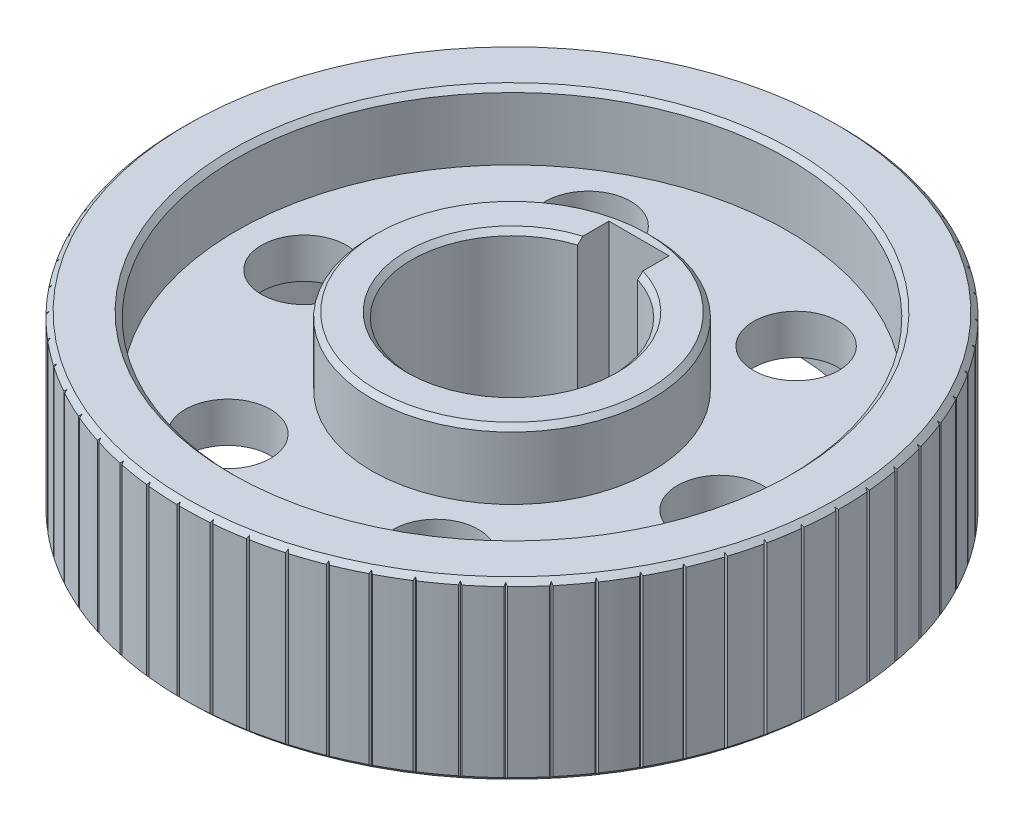
SolidWorks part; units mm, degrees
ref_plane "前视基准面" through (0, 0, 0) normal (0, 0, 1) x (1, 0, 0)
ref_plane "上视基准面" through (0, 0, 0) normal (0, 1, 0) x (1, 0, 0)
ref_plane "右视基准面" through (0, 0, 0) normal (1, 0, 0) x (0, 0, -1)
other "Configuration Table"
sketch "草图2" plane through (0, 0, 0) normal (0, 1, 0) x (1, 0, 0)
  circle A0 centre (0, 0) radius 65.7475
extrude "凸台-拉伸1" add sketch "草图2" along normal blind 35
sketch "草图3" plane through (0, 35, 0) normal (0, 1, 0) x (1, 0, 0)
  line L1 (0, 25.3371) -> (6, 25.3371)
  line L2 (0, 25.3371) -> (-6, 25.3371)
  line L3 (-6, 25.3371) -> (-6, 19.0788)
  line L4 (6, 25.3371) -> (6, 19.0788)
  circle A2 centre (-20.75, 35.9401) radius 8.5
  circle A3 centre (0, 0) radius 65.7475
  circle A4 centre (0, 0) radius 65.7475
  circle A5 centre (20.75, 35.9401) radius 8.5
  circle A6 centre (41.5, 0) radius 8.5
  circle A7 centre (20.75, -35.9401) radius 8.5
  circle A8 centre (-20.75, -35.9401) radius 8.5
  circle A9 centre (-41.5, 0) radius 8.5
  circle A10 centre (0, 0) radius 28
  circle A11 centre (0, 0) radius 55
  arc A12 (-6, 19.0788) -> (6, 19.0788) centre (0, 0) ccw
  dimension "D1" = 0
  dimension "D3" = 6
extrude "切除-拉伸1" cut sketch "草图3" against normal through all both and the other way through all contours L3 A12 L4 L1 L2 region at (0, 35, -1.1506)
extrude "切除-拉伸2" cut sketch "草图3<6>" against normal blind 13.5 and the other way through all contours A11 A2 A5 A6 A7 A8 A9 A10 region at (-53.4444, 35, 0)
sketch "草图3<6>" plane through (0, 35, 0) normal (0, 1, 0) x (1, 0, 0) same geometry as "草图3"
extrude "切除-拉伸3" cut sketch "草图3<7>" against normal through all both and the other way through all contours A2 | A9 | A8 | A6 | A5 | A7 region at (-20.75, 35, -35.9401) region at (20.75, 35, -35.9401) region at (41.5, 35, 0) region at (-20.75, 35, 35.9401) region at (-41.5, 35, 0)
sketch "草图3<7>" plane through (0, 35, 0) normal (0, 1, 0) x (1, 0, 0) same geometry as "草图3"
ref_plane "基准面1" through (0, 17.5, 0) normal (0, 1, 0) x (1, 0, 0)
mirror "镜向1" about plane through (0, 17.5, 0) normal (0, 1, 0) of "切除-拉伸2"
chamfer "倒角2" distance 1 angle 45 8 edges at (0, 35, 28) (0, 35, 55) (0, 35, 65.7475) (0, 0, 65.7475) (0, 0, 28) (0, 0, 20) (0, 0, 55)
sketch "草图4" plane through (0, 35, 0) normal (0, 1, 0) x (1, 0, 0)
  line L0 (0, 0) -> (-0.9608, 84.036) construction
  line L1 (0, 0) -> (30.9039, 88.026) construction
  line L2 (0, 0) -> (1.2765, 94.3711) construction
  line L3 (-0.7068, 61.8255) -> (19.2462, 54.8205)
  circle A0 centre (0, 0) radius 61.8295
  circle A1 centre (0, 0) radius 66
  circle A2 centre (0, 0) radius 64.4075 construction
  circle A7 centre (19.2462, 54.8205) radius 21.147
  circle A8 centre (-17.7563, 55.321) radius 21.147
  point P5 (-0.7068, 61.8255)
  dimension "D1" = 20
  dimension "D2" = 1.43
extrude "切除-拉伸6" cut sketch "草图4" against normal through all contours A1 A8 A7 region at (0.8896, 35, -65.7669)
sketch "草图8" plane through (0, 0, 0) normal (1, 0, 0) x (0, 0, -1)
  line L0 (0, 0) -> (0, 41.0373)
pattern_circular "阵列(圆周)2" count 64 over 360 about axis through (0, 0, 0) along (0, 1, 0) of "切除-拉伸6"
